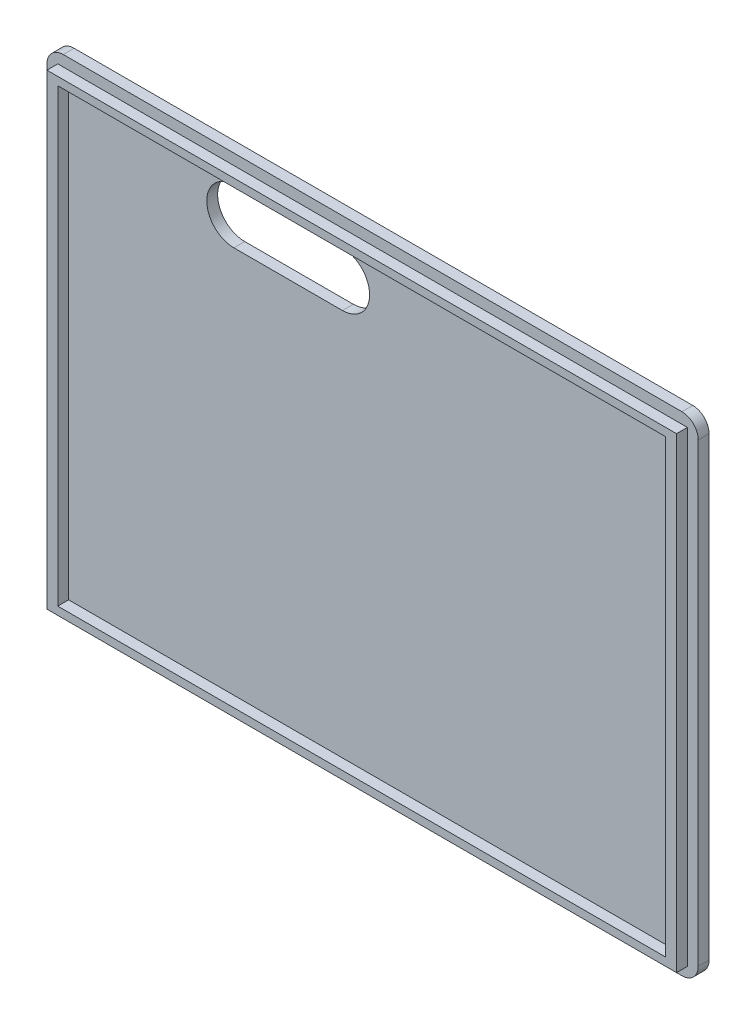
SolidWorks part; units mm, degrees
ref_plane "Plan de face" through (0, 0, 0) normal (0, 0, 1) x (1, 0, 0)
ref_plane "Plan de dessus" through (0, 0, 0) normal (0, 1, 0) x (1, 0, 0)
ref_plane "Plan de droite" through (0, 0, 0) normal (1, 0, 0) x (0, 0, -1)
sketch "Esquisse1" plane through (0, 0, 0) normal (0, 0, 1) x (1, 0, 0)
  line L1 (60, -45) -> (-60, -45)
  line L2 (60, -45) -> (60, 45)
  line L3 (60, 45) -> (-60, 45)
  line L4 (-60, -45) -> (-60, 45)
  line L5 (60, -45) -> (-60, 45) construction
  line L6 (60, 45) -> (-60, -45) construction
  point P0 (0, 0)
  dimension "D1" = 120
  dimension "D2" = 90
extrude "Boss.-Extru.1" add sketch "Esquisse1" along normal blind 2
sketch "Esquisse2" plane through (0, 0, 2) normal (0, 0, 1) x (1, 0, 0)
  line L1 (58, -43) -> (-58, -43)
  line L2 (58, -43) -> (58, 43)
  line L3 (58, 43) -> (-58, 43)
  line L4 (-58, -43) -> (-58, 43)
  line L5 (58, -43) -> (-58, 43) construction
  line L6 (58, 43) -> (-58, -43) construction
  line L7 (56, -41.5172) -> (-56, -41.5172)
  line L8 (56, -41.5172) -> (56, 41.5172)
  line L9 (56, 41.5172) -> (-56, 41.5172)
  line L10 (-56, -41.5172) -> (-56, 41.5172)
  line L11 (56, -41.5172) -> (-56, 41.5172) construction
  line L12 (56, 41.5172) -> (-56, -41.5172) construction
  point P0 (0, 0)
  point P6 (0, 0)
  dimension "D1" = 116
  dimension "D2" = 86
  dimension "D3" = 2
extrude "Boss.-Extru.2" add sketch "Esquisse2" along normal blind 2
sketch "Esquisse3" plane through (0, 0, 0) normal (0, 0, -1) x (-1, 0, 0)
  line L0 (5.5484, 34.875) -> (25.5484, 34.875) construction
  line L1 (5.5484, 39.875) -> (25.5484, 39.875)
  line L2 (5.5484, 29.875) -> (25.5484, 29.875)
  arc A0 (5.5484, 39.875) -> (5.5484, 29.875) centre (5.5484, 34.875) ccw
  arc A1 (25.5484, 29.875) -> (25.5484, 39.875) centre (25.5484, 34.875) ccw
  point P2 (15.5484, 34.875)
  point P7 (17.5428, 35.9444)
  point P8 (6.4193, 35.7473)
  point P9 (24.2905, 34.5856)
  point P10 (15.5484, 34.875)
  dimension "D1" = 20
  dimension "D2" = 10
extrude "Enlèv. mat.-Extru.1" cut sketch "Esquisse3" against normal blind 2
fillet "Congé1" radius 3 4 edges at (60, 45, 1) (-60, -45, 1) (-60, 45, 1) (60, -45, 1)
